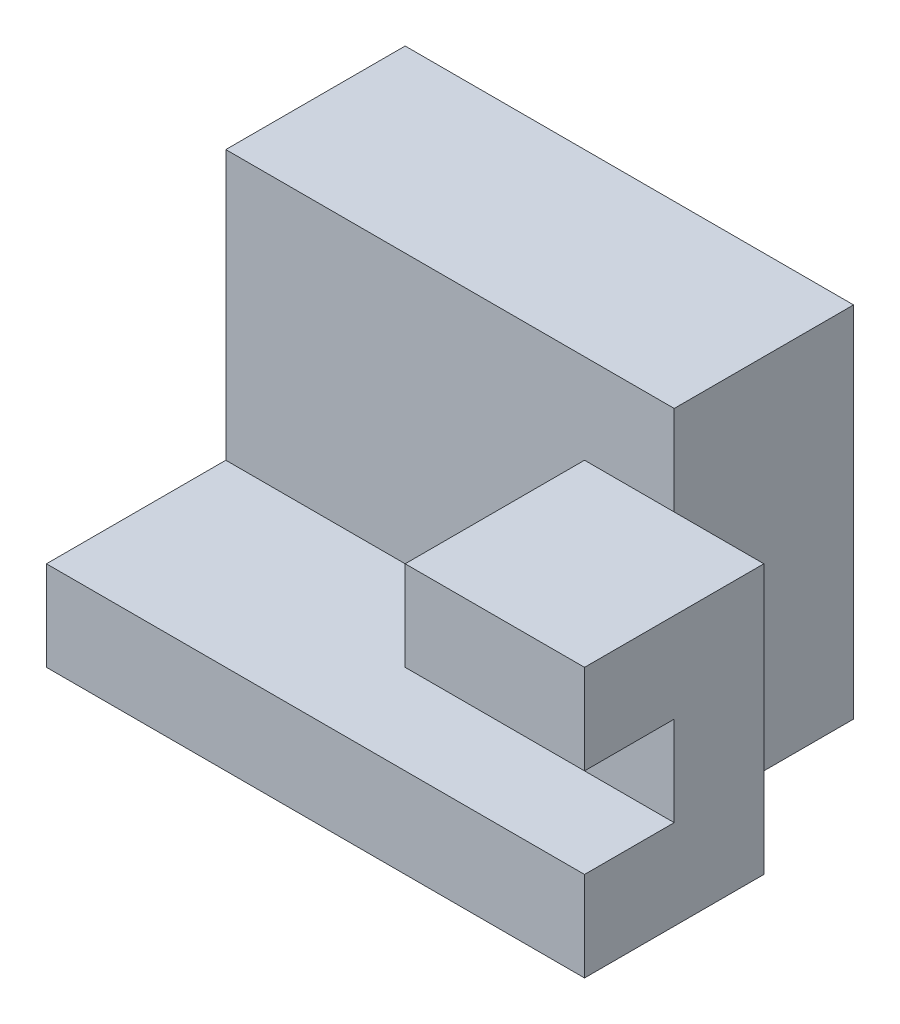
SolidWorks part; units mm, degrees
ref_plane "Front Plane" through (0, 0, 0) normal (0, 0, 1) x (1, 0, 0)
ref_plane "Top Plane" through (0, 0, 0) normal (0, 1, 0) x (1, 0, 0)
ref_plane "Right Plane" through (0, 0, 0) normal (1, 0, 0) x (0, 0, -1)
sketch "Sketch1" plane through (0, 0, 0) normal (1, 0, 0) x (0, 0, -1)
  line L0 (20, 30) -> (0, 30)
  line L1 (0, 0) -> (20, 0)
  line L2 (0, 0) -> (0, 10)
  line L3 (0, 10) -> (20, 10)
  line L4 (20, 0) -> (20, 10)
  line L5 (20, 0) -> (40, 0)
  line L6 (20, 0) -> (20, 40)
  line L7 (20, 40) -> (40, 40)
  line L8 (40, 0) -> (40, 40)
  line L9 (0, 30) -> (0, 20)
  line L10 (0, 20) -> (10, 20)
  line L11 (10, 20) -> (10, 10)
  dimension "D1" = 40
  dimension "D2" = 40
  dimension "D3" = 20
  dimension "D4" = 10
  dimension "D5" = 30
  dimension "D6" = 10
  dimension "D7" = 10
extrude "Boss-Extrude1" add sketch "Sketch1" against normal blind 50 contours L5 L8 L7 L6 L4 | L1 L4 L3 L2 region at (0, 20, -30) region at (0, 5, -10)
extrude "Boss-Extrude2" add sketch "Sketch1<3>" along normal mid plane 20 contours L1 L4 L3 L2 | L10 L11 L3 L6 L0 L9 region at (0, 21.6667, -11.6667) region at (0, 5, -10)
sketch "Sketch1<3>" plane through (0, 0, 0) normal (1, 0, 0) x (0, 0, -1) same geometry as "Sketch1"
